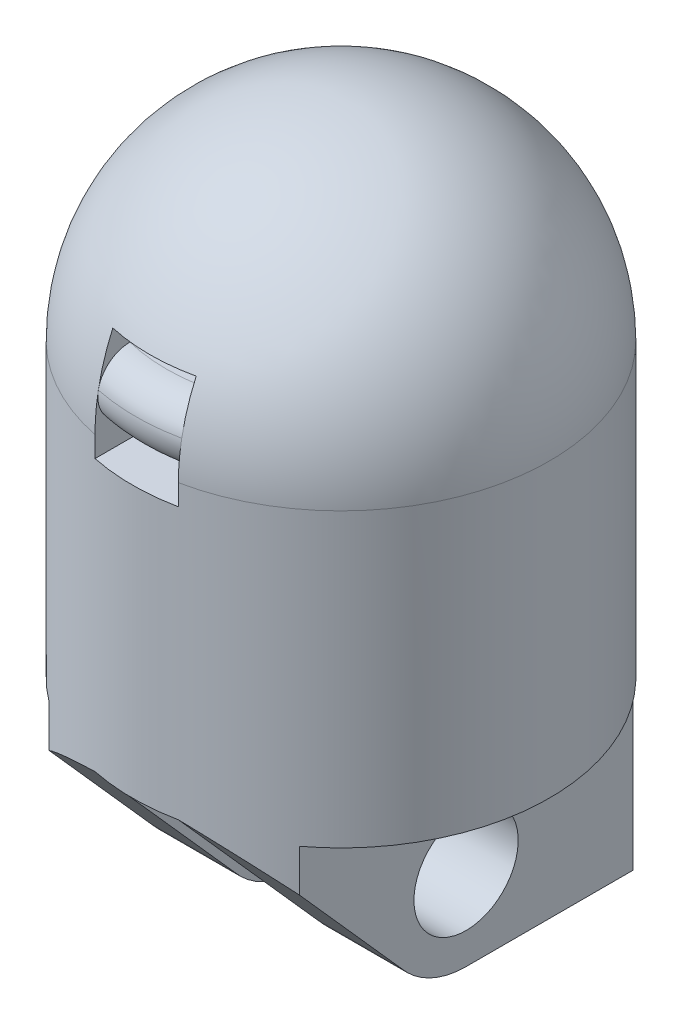
SolidWorks part; units mm, degrees
ref_plane "Front Plane" through (0, 0, 0) normal (0, 0, 1) x (1, 0, 0)
ref_plane "Top Plane" through (0, 0, 0) normal (0, 1, 0) x (1, 0, 0)
ref_plane "Right Plane" through (0, 0, 0) normal (1, 0, 0) x (0, 0, -1)
sketch "Sketch1" plane through (0, 0, 0) normal (0, 0, 1) x (1, 0, 0)
  line L0 (0, 0) -> (0, 5.6026)
  line L1 (0, 0) -> (-12.7, 0)
  line L2 (-12.7, 0) -> (-12.7, 29.21)
  line L6 (0, 5.6026) -> (-2.54, 5.6026)
  line L7 (-2.54, 22.86) -> (-2.54, 5.6026)
  line L8 (0, 36.0492) -> (0, 41.91)
  arc A0 (0, 41.91) -> (-12.7, 29.21) centre (0, 29.21) ccw
  arc A1 (-2.54, 22.86) -> (0, 36.0492) centre (0, 29.21) cw
  dimension "D3" = 25.4
  dimension "D1" = 41.91
  dimension "D2" = 12.7
  dimension "D4" = 2.54
revolve "Revolve1" add sketch "Sketch1" angle 360 about L0
sketch "Sketch2" plane through (0, 0, 0) normal (0, -1, 0) x (1, 0, 0)
  line L0 (-2.54, 12.4434) -> (-2.54, -12.4434)
  line L1 (-7.62, 10.16) -> (-7.62, -10.16)
  line L2 (2.54, 12.4434) -> (2.54, -12.4434)
  line L3 (7.62, 10.16) -> (7.62, -10.16)
  circle A0 centre (0, 0) radius 12.7 construction
  arc A1 (-7.62, 10.16) -> (-7.62, -10.16) centre (0, 0) ccw
  arc A2 (-2.54, -12.4434) -> (2.54, -12.4434) centre (0, 0) ccw
  arc A3 (7.62, -10.16) -> (7.62, 10.16) centre (0, 0) ccw
  arc A4 (2.54, 12.4434) -> (-2.54, 12.4434) centre (0, 0) ccw
  dimension "D1" = 2.54
  dimension "D2" = 5.08
  dimension "D3" = 2.54
  dimension "D4" = 5.08
extrude "Cut-Extrude1" cut sketch "Sketch2" against normal blind 11.43
sketch "Sketch3" plane through (-7.62, 0, 0) normal (-1, 0, 0) x (0, 0, 1)
  line L0 (0, -13.97) -> (0, 13.97) construction
  line L1 (-10.16, 0) -> (10.16, 0) construction
  circle A0 centre (0, 5.08) radius 3.175
  dimension "D2" = 6.35
  dimension "D1" = 5.08
extrude "Cut-Extrude2" cut sketch "Sketch3" against normal through all
sketch "Sketch4" plane through (-2.54, 0, 0) normal (1, 0, 0) x (0, 0, -1)
  line L0 (-12.4434, 11.43) -> (-3.9413, 1.875)
  line L1 (0, 0) -> (-12.4434, 0)
  line L2 (-12.4434, 11.43) -> (-12.4434, 0)
  arc A0 (0, 0) -> (-3.9413, 1.875) centre (0, 5.08) cw
extrude "Cut-Extrude3" cut sketch "Sketch4" against normal through all both and the other way through all
sketch "Sketch7" plane through (0, 0, 0) normal (0, 0, 1) x (1, 0, 0)
  line L5 (12.7, 29.21) -> (-12.7, 29.21) construction
  line L10 (-2.54, 29.21) -> (2.54, 29.21)
  line L11 (-2.54, 29.21) -> (-2.54, 27.94)
  line L12 (-2.54, 27.94) -> (2.54, 27.94)
  line L13 (2.54, 29.21) -> (2.54, 27.94)
  line L15 (-2.54, 33.02) -> (2.54, 33.02)
  line L16 (-2.54, 33.02) -> (-2.54, 34.29)
  line L17 (-2.54, 34.29) -> (2.54, 34.29)
  line L18 (2.54, 33.02) -> (2.54, 34.29)
  dimension "D1" = 1.27
  dimension "D2" = 1.27
  dimension "D3" = 3.81
extrude "Cut-Extrude5" cut sketch "Sketch7" against normal through all both and the other way through all
fillet "Fillet1" radius 1.905 4 edges at (0, 29.21, -12.7) (0, 33.02, -12.115) (0, 29.21, 12.7) (0, 33.02, 12.115)
